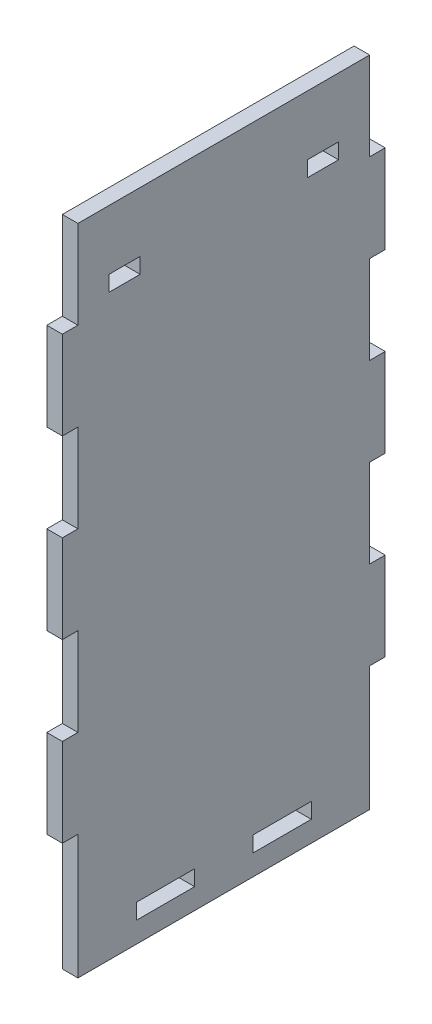
SolidWorks part; units mm, degrees
ref_plane "Front Plane" through (0, 0, 0) normal (0, 0, 1) x (1, 0, 0)
ref_plane "Top Plane" through (0, 0, 0) normal (0, 1, 0) x (1, 0, 0)
ref_plane "Right Plane" through (0, 0, 0) normal (1, 0, 0) x (0, 0, -1)
sketch "Sketch1" plane through (0, 0, 0) normal (1, 0, 0) x (0, 0, -1)
  line L1 (-56.25, -119) -> (56.25, -119)
  line L2 (-56.25, -119) -> (-56.25, 119)
  line L3 (-56.25, 119) -> (56.25, 119)
  line L4 (56.25, -119) -> (56.25, 119)
  line L5 (-56.25, -119) -> (56.25, 119) construction
  line L6 (-56.25, 119) -> (56.25, -119) construction
  point P0 (0, 0)
  dimension "D1" = 238
  dimension "D2" = 112.5
extrude "Boss-Extrude1" add sketch "Sketch1" along normal blind 6
sketch "Sketch4" plane through (0, -119, 0) normal (0, -1, 0) x (1, 0, 0)
  line L0 (6, 56.25) -> (6, -56.25) construction
  line L1 (0, -56.25) -> (6, -56.25)
  line L2 (0, -56.25) -> (0, -33.75)
  line L3 (0, -33.75) -> (6, -33.75)
  line L4 (6, -56.25) -> (6, -33.75)
  line L5 (0, 56.25) -> (0, -56.25) construction
  line L6 (6, -33.75) -> (0, -33.75) construction
  line L7 (6, -33.75) -> (6, -11.25) construction
  line L8 (6, -11.25) -> (0, -11.25) construction
  line L9 (0, -33.75) -> (0, -11.25) construction
  line L11 (6, 11.25) -> (0, 11.25)
  line L12 (6, 11.25) -> (6, -11.25)
  line L13 (6, -11.25) -> (0, -11.25)
  line L14 (0, 11.25) -> (0, -11.25)
  line L15 (0, 11.25) -> (6, 11.25) construction
  line L16 (0, 11.25) -> (0, 33.75) construction
  line L17 (0, 33.75) -> (6, 33.75) construction
  line L18 (6, 11.25) -> (6, 33.75) construction
  line L19 (6, 33.75) -> (0, 33.75)
  line L20 (6, 33.75) -> (6, 56.25)
  line L21 (6, 56.25) -> (0, 56.25)
  line L22 (0, 33.75) -> (0, 56.25)
extrude "Boss-Extrude2" add sketch "Sketch4" along normal blind 6
sketch "Sketch5" plane through (0, 0, -56.25) normal (0, 0, -1) x (-1, 0, 0)
  line L0 (0, -125) -> (0, 119) construction
  line L1 (-6, -119) -> (0, -119)
  line L2 (-6, -119) -> (-6, -85)
  line L3 (-6, -85) -> (0, -85)
  line L4 (0, -119) -> (0, -85)
  line L5 (-6, -125) -> (-6, 119) construction
  line L6 (0, -85) -> (-6, -85)
  line L7 (0, -85) -> (0, -51)
  line L8 (0, -51) -> (-6, -51)
  line L9 (-6, -85) -> (-6, -51)
  line L10 (-6, -119) -> (-6, -125) construction
  line L11 (-6, -51) -> (0, -51)
  line L12 (-6, -51) -> (-6, -17)
  line L13 (-6, -17) -> (0, -17)
  line L14 (0, -51) -> (0, -17)
  line L15 (0, -17) -> (-6, -17)
  line L16 (0, -17) -> (0, 17)
  line L17 (0, 17) -> (-6, 17)
  line L18 (-6, -17) -> (-6, 17)
  line L19 (-6, 17) -> (0, 17)
  line L20 (-6, 17) -> (-6, 51)
  line L21 (-6, 51) -> (0, 51)
  line L22 (0, 17) -> (0, 51)
  line L23 (0, 51) -> (-6, 51)
  line L24 (0, 51) -> (0, 85)
  line L25 (0, 85) -> (-6, 85)
  line L26 (-6, 51) -> (-6, 85)
  line L27 (-6, 85) -> (0, 85)
  line L28 (-6, 85) -> (-6, 119)
  line L29 (-6, 119) -> (0, 119)
  line L30 (0, 85) -> (0, 119)
  line L31 (0, -125) -> (-6, -125) construction
  line M17 (0, -125) -> (0, 119)
  line M19 (-6, 119) -> (-6, -125)
extrude "Boss-Extrude3" add sketch "Sketch5" along normal blind 6 contours L8 L3 M17 M19 | L17 L13 M17 M19 | L25 L21 M17 M19 region at (3, -68, -56.25) region at (3, 0, -56.25) region at (3, 68, -56.25)
mirror "Mirror1" about plane through (0, 0, 0) normal (0, 0, 1) of "Boss-Extrude3"
sketch "Sketch6" plane through (6, 0, 0) normal (1, 0, 0) x (0, 0, -1)
  line L0 (-32.25, 90) -> (32.25, 90)
  line L1 (-44.25, 90) -> (-32.25, 90)
  line L2 (-44.25, 90) -> (-44.25, 96)
  line L3 (-44.25, 96) -> (-32.25, 96)
  line L4 (-32.25, 90) -> (-32.25, 96)
  line L5 (32.25, 96) -> (44.25, 96)
  line L6 (32.25, 96) -> (32.25, 90)
  line L7 (32.25, 90) -> (44.25, 90)
  line L8 (44.25, 96) -> (44.25, 90)
  line L9 (0, 90) -> (0, 0)
  line L10 (-44.25, 90) -> (-44.25, 96) construction
  line L11 (-32.25, 96) -> (-44.25, 96) construction
  line L12 (32.25, 90) -> (-32.25, 90) construction
  line L13 (56.25, 119) -> (-56.25, 119) construction
  point P10 (0, 0)
  point P18 (-44.25, 92.0126)
  point P19 (0, 0)
  point P20 (0, 0)
  dimension "D1" = 23
extrude "Cut-Extrude1" cut sketch "Sketch6" against normal blind 800 contours L1 L4 L3 L2 | L8 L5 L6 L7 region at (6, 93, -38.25) region at (6, 93, 38.25)
sketch "Sketch7" plane through (0, -125, 0) normal (0, -1, 0) x (1, 0, 0)
  line L1 (0, 56.25) -> (6, 56.25)
  line L2 (0, 56.25) -> (0, -56.25)
  line L3 (0, -56.25) -> (6, -56.25)
  line L4 (6, 56.25) -> (6, -56.25)
extrude "Boss-Extrude4" add sketch "Sketch7" along normal blind 8
